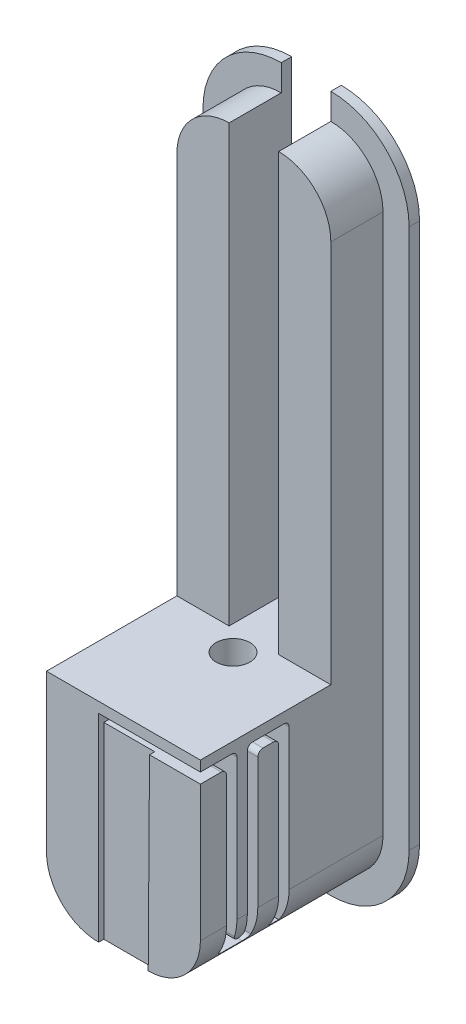
SolidWorks part; units mm, degrees
ref_plane "Front Plane" through (0, 0, 0) normal (0, 0, 1) x (1, 0, 0)
ref_plane "Top Plane" through (0, 0, 0) normal (0, 1, 0) x (1, 0, 0)
ref_plane "Right Plane" through (0, 0, 0) normal (1, 0, 0) x (0, 0, -1)
sketch "Sketch1" plane through (0, 0, 0) normal (0, 0, 1) x (1, 0, 0)
  line L1 (-4.75, -61.75) -> (4.75, -61.75)
  line L2 (-14.75, -51.75) -> (-14.75, 51.75)
  line L3 (-4.75, 61.75) -> (4.75, 61.75)
  line L4 (14.75, -51.75) -> (14.75, 51.75)
  line L5 (-14.75, -61.75) -> (14.75, 61.75) construction
  line L6 (-14.75, 61.75) -> (14.75, -61.75) construction
  arc A0 (-4.75, -61.75) -> (-14.75, -51.75) centre (-4.75, -51.75) cw
  arc A1 (4.75, -61.75) -> (14.75, -51.75) centre (4.75, -51.75) ccw
  arc A2 (4.75, 61.75) -> (14.75, 51.75) centre (4.75, 51.75) cw
  arc A3 (-14.75, 51.75) -> (-4.75, 61.75) centre (-4.75, 51.75) cw
  point P0 (0, 0)
  dimension "D3" = 10
  dimension "D1" = 29.5
  dimension "D2" = 123.5
extrude "Boss-Extrude1" add sketch "Sketch1" along normal blind 10
sketch "Sketch3" plane through (0, 0, 10) normal (0, 0, 1) x (1, 0, 0)
  line L0 (14.75, -21.75) -> (-14.75, -21.75)
  line L4 (-4.75, -61.75) -> (4.75, -61.75)
  line L5 (14.75, -51.75) -> (14.75, 51.75)
  line L6 (4.75, 61.75) -> (-4.75, 61.75)
  line L7 (-14.75, 51.75) -> (-14.75, -51.75)
  line L8 (-4.75, -61.75) -> (4.75, -61.75)
  line L9 (14.75, -51.75) -> (14.75, 51.75)
  line L10 (4.75, 61.75) -> (-4.75, 61.75)
  line L11 (-14.75, 51.75) -> (-14.75, -51.75)
  arc A4 (-14.75, -51.75) -> (-4.75, -61.75) centre (-4.75, -51.75) ccw
  arc A5 (4.75, -61.75) -> (14.75, -51.75) centre (4.75, -51.75) ccw
  arc A6 (14.75, 51.75) -> (4.75, 61.75) centre (4.75, 51.75) ccw
  arc A7 (-4.75, 61.75) -> (-14.75, 51.75) centre (-4.75, 51.75) ccw
  arc A8 (-14.75, -51.75) -> (-4.75, -61.75) centre (-4.75, -51.75) ccw
  arc A9 (4.75, -61.75) -> (14.75, -51.75) centre (4.75, -51.75) ccw
  arc A10 (14.75, 51.75) -> (4.75, 61.75) centre (4.75, 51.75) ccw
  arc A11 (-4.75, 61.75) -> (-14.75, 51.75) centre (-4.75, 51.75) ccw
  arc M9 (-14.75, -51.75) -> (-4.75, -61.75) centre (-4.75, -51.75) ccw
  line M10 (-4.75, -61.75) -> (4.75, -61.75)
  arc M11 (4.75, -61.75) -> (14.75, -51.75) centre (4.75, -51.75) ccw
  line M12 (14.75, -51.75) -> (14.75, 51.75)
  line M16 (-14.75, 51.75) -> (-14.75, -51.75)
  dimension "D2" = 40
  dimension "D1" = 0
extrude "Boss-Extrude2" add sketch "Sketch3" along normal blind 25 contours L0 M12 M16 M9 M10 M11
sketch "Sketch4" plane through (14.75, 0, 0) normal (1, 0, 0) x (0, 0, -1)
  line L0 (-34, -74.3985) -> (-34, -25.75)
  line L1 (-34, -25.75) -> (-30, -25.75)
  line L2 (-30, -25.75) -> (-30, -57.75)
  line L3 (-30, -57.75) -> (-24, -57.75)
  line L4 (-24, -57.75) -> (-24, -25.75)
  line L5 (-24, -25.75) -> (-20, -25.75)
  line L6 (-20, -25.75) -> (-20, -57.75)
  line L7 (-35, -21.75) -> (-10, -21.75) construction
  line L8 (-35, -61.75) -> (0, -61.75) construction
  line L9 (-35, -51.75) -> (-35, -21.75) construction
  dimension "D1" = 4
  dimension "D2" = 4
  dimension "D3" = 1
  dimension "D4" = 4
extrude "Cut-Extrude-Thin1" cut sketch "Sketch4" against normal up to vertex (19.5 mm away) and the other way through all thin thin type one direction reverse wall 2
sketch "Sketch5" plane through (0, 0, 0) normal (0, 0, -1) x (-1, 0, 0)
  line L0 (-4.75, 61.75) -> (4.75, 61.75) construction
  line L1 (4.75, 61.75) -> (-4.75, 61.75)
  line L2 (4.75, 61.75) -> (4.75, -21.75)
  line L3 (4.75, -21.75) -> (-4.75, -21.75)
  line L4 (-4.75, 61.75) -> (-4.75, -21.75)
  arc A0 (-4.75, 61.75) -> (-14.75, 51.75) centre (-4.75, 51.75) ccw construction
  dimension "D1" = 83.5
extrude "Cut-Extrude1" cut sketch "Sketch5" against normal blind 25
fillet "Fillet2" radius 1 10 edges at (5, -25.75, 24) (4, -57.75, 30) (4, -57.75, 24) (5, -25.75, 20) (5, -23.75, 18) (5, -23.75, 28) (5, -23.75, 26) (4.5826, -55.75, 26) (4.5826, -55.75, 28) (5, -25.75, 30)
ref_plane "Plane1" through (0, 0, 10) normal (0, 0, 1) x (1, 0, 0)
sketch "Sketch8" plane through (0, -21.75, 0) normal (0, 1, 0) x (1, 0, 0)
  line L0 (14.75, -10) -> (4.75, -10) construction
  circle A0 centre (0, -14) radius 3.25
  dimension "D1" = 6.5
  dimension "D2" = 4
extrude "Cut-Extrude2" cut sketch "Sketch8" against normal blind 54
sketch "Sketch9" plane through (0, -61.75, 0) normal (0, -1, 0) x (-1, 0, 0)
  line L1 (0, -9.3812) -> (-4, -11.6906)
  line L2 (-4, -11.6906) -> (-4, -16.3094)
  line L3 (-4, -16.3094) -> (0, -18.6188)
  line L4 (0, -18.6188) -> (4, -16.3094)
  line L5 (4, -16.3094) -> (4, -11.6906)
  line L6 (4, -11.6906) -> (0, -9.3812)
  circle A0 centre (0, -14) radius 4 construction
  dimension "D1" = 8
extrude "Cut-Extrude3" cut sketch "Sketch9" against normal offset from surface (30 mm away) 10 up to face at (-3.25, -21.75, 14)
sketch "Sketch11" plane through (0, 0, 0) normal (0, 0, -1) x (-1, 0, 0)
  line L0 (19.75, -51.75) -> (19.75, 51.75)
  line L1 (0, 65.9781) -> (0, 65.9781)
  line L2 (0, 65.9781) -> (0, 65.9781)
  line L3 (0, 65.9781) -> (0, 65.9781)
  line L4 (-19.75, 51.75) -> (-19.75, -51.75)
  line L5 (-4.75, -66.75) -> (4.75, -66.75)
  line L6 (4.75, 61.75) -> (4.75, -21.75)
  line L7 (4.75, -21.75) -> (-4.75, -21.75)
  line L8 (-4.75, -21.75) -> (-4.75, 61.75)
  line L9 (-14.75, 51.75) -> (-14.75, -51.75)
  line L10 (-4.75, -61.75) -> (4.75, -61.75)
  line L11 (14.75, -51.75) -> (14.75, 51.75)
  line L12 (4.75, 61.75) -> (4.75, -21.75)
  line L13 (4.75, -21.75) -> (-4.75, -21.75)
  line L14 (-4.75, -21.75) -> (-4.75, 61.75)
  line L15 (-14.75, 51.75) -> (-14.75, -51.75)
  line L16 (-4.75, -61.75) -> (4.75, -61.75)
  line L17 (14.75, -51.75) -> (14.75, 51.75)
  line L19 (4.75, 61.75) -> (4.75, 66.75)
  line L20 (-4.75, 61.75) -> (-4.75, 66.75)
  arc A0 (19.75, 51.75) -> (4.75, 66.75) centre (4.75, 51.75) ccw
  arc A1 (-4.75, 66.75) -> (-19.75, 51.75) centre (-4.75, 51.75) ccw
  arc A2 (-19.75, -51.75) -> (-4.75, -66.75) centre (-4.75, -51.75) ccw
  arc A3 (4.75, -66.75) -> (19.75, -51.75) centre (4.75, -51.75) ccw
  arc A4 (-4.75, 61.75) -> (-14.75, 51.75) centre (-4.75, 51.75) ccw
  arc A5 (-14.75, -51.75) -> (-4.75, -61.75) centre (-4.75, -51.75) ccw
  arc A6 (4.75, -61.75) -> (14.75, -51.75) centre (4.75, -51.75) ccw
  arc A7 (14.75, 51.75) -> (4.75, 61.75) centre (4.75, 51.75) ccw
  arc A8 (-4.75, 61.75) -> (-14.75, 51.75) centre (-4.75, 51.75) ccw
  arc A9 (-14.75, -51.75) -> (-4.75, -61.75) centre (-4.75, -51.75) ccw
  arc A10 (4.75, -61.75) -> (14.75, -51.75) centre (4.75, -51.75) ccw
  arc A11 (14.75, 51.75) -> (4.75, 61.75) centre (4.75, 51.75) ccw
  arc A13 (19.75, 51.75) -> (0, 65.9781) centre (4.75, 51.75) ccw construction
  arc A14 (0, 65.9781) -> (-19.75, 51.75) centre (-4.75, 51.75) ccw construction
  line M12 (4.75, 61.75) -> (4.75, -21.75)
  line M13 (4.75, -21.75) -> (-4.75, -21.75)
  line M14 (-4.75, -21.75) -> (-4.75, 61.75)
  arc M15 (-4.75, 61.75) -> (-14.75, 51.75) centre (-4.75, 51.75) ccw
  line M16 (-14.75, 51.75) -> (-14.75, -51.75)
  arc M17 (-14.75, -51.75) -> (-4.75, -61.75) centre (-4.75, -51.75) ccw
  line M18 (-4.75, -61.75) -> (4.75, -61.75)
  arc M19 (4.75, -61.75) -> (14.75, -51.75) centre (4.75, -51.75) ccw
  line M20 (14.75, -51.75) -> (14.75, 51.75)
  arc M21 (14.75, 51.75) -> (4.75, 61.75) centre (4.75, 51.75) ccw
  dimension "D1" = 0
  dimension "D2" = 5
extrude "Boss-Extrude5" add sketch "Sketch11" along normal blind 2 contours L5 A3 L0 A0 L19 L20 A1 L4 A2 M21 M20 M19 M18 M17 M16 M15 | M21 M12 M13 M14 M15 M16 M17 M18 M19 M20
sketch "Sketch12" plane through (0, 0, 34) normal (0, 0, 1) x (1, 0, 0)
  line L0 (4.75, -61.75) -> (5, -25.75)
  line L4 (14.75, -51.75) -> (14.75, -25.75)
  line L5 (14.75, -25.75) -> (-4.75, -25.75)
  line L6 (-4.75, -25.75) -> (-4.75, -61.75)
  line L7 (-4.75, -61.75) -> (4.75, -61.75)
  line L8 (14.75, -51.75) -> (14.75, -25.75)
  line L9 (14.75, -25.75) -> (-4.75, -25.75)
  line L10 (-4.75, -25.75) -> (-4.75, -61.75)
  line L11 (-4.75, -61.75) -> (4.75, -61.75)
  arc A1 (4.75, -61.75) -> (14.75, -51.75) centre (4.75, -51.75) ccw
  arc A2 (4.75, -61.75) -> (14.75, -51.75) centre (4.75, -51.75) ccw
  arc M6 (4.75, -61.75) -> (14.75, -51.75) centre (4.75, -51.75) ccw
  line M7 (14.75, -51.75) -> (14.75, -25.75)
  line M8 (14.75, -25.75) -> (-4.75, -25.75)
  dimension "D1" = 0
extrude "Boss-Extrude6" add sketch "Sketch12" along normal up to surface (1 mm away) contours L0 M6 M7 M8 up to face at (-1.9285, -34.4285, 35)
